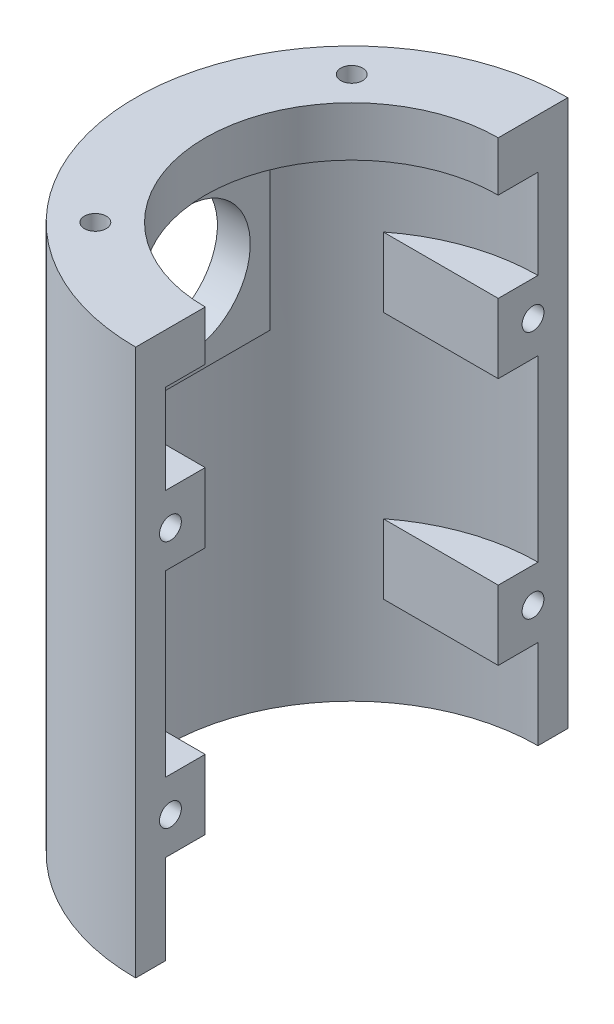
SolidWorks part; units mm, degrees
ref_plane "正面" through (0, 0, 0) normal (0, 0, 1) x (1, 0, 0)
ref_plane "平面" through (0, 0, 0) normal (0, 1, 0) x (1, 0, 0)
ref_plane "右側面" through (0, 0, 0) normal (1, 0, 0) x (0, 0, -1)
sketch "ｽｹｯﾁ1" plane through (0, 0, 0) normal (0, 1, 0) x (1, 0, 0)
  line L0 (0, -21.75) -> (0, -14.75)
  line L1 (0, -14.75) -> (0, 14.75) construction
  line L2 (0, 14.75) -> (0, 21.75)
  arc A0 (0, 21.75) -> (0, -21.75) centre (0, 0) ccw
  arc A1 (0, 14.75) -> (0, -14.75) centre (0, 0) ccw
  dimension "D1" = 14.75
  dimension "D2" = 7
extrude "ﾎﾞｽ - 押し出し1" add sketch "ｽｹｯﾁ1" along normal blind 55
sketch "ｽｹｯﾁ2" plane through (0, 55, 0) normal (0, 1, 0) x (1, 0, 0)
  circle A0 centre (0, 0) radius 14.75
  circle A1 centre (0, 0) radius 18.75
  arc A2 (0, 14.75) -> (0, -14.75) centre (0, 0) ccw construction
  arc A3 (0, 21.75) -> (0, -21.75) centre (0, 0) ccw construction
  dimension "D1" = 3
extrude "ｶｯﾄ - 押し出し1" cut sketch "ｽｹｯﾁ2" against normal through all from offset 5 offset against normal yes
sketch "ｽｹｯﾁ4" plane through (0, 0, 0) normal (1, 0, 0) x (0, 0, -1)
  line L0 (-14.75, 12.5) -> (-21.75, 12.5) construction
  line L1 (-21.75, 41) -> (-21.75, 34)
  line L2 (-18.75, 50) -> (-14.75, 50) construction
  line L3 (21.75, 55) -> (21.75, 0) construction
  line L4 (18.75, 50) -> (18.75, 0) construction
  line L5 (-21.75, 16) -> (-14.75, 16)
  line L6 (-14.75, 16) -> (-14.75, 9)
  line L7 (-14.75, 9) -> (-21.75, 9)
  line L8 (-21.75, 9) -> (-21.75, 16)
  line L9 (-21.75, 50) -> (21.75, 50) construction
  line L10 (0, 25) -> (-21.75, 25) construction
  line L11 (0, 25) -> (21.75, 25) construction
  line L12 (-21.75, 37.5) -> (21.75, 37.5) construction
  line L13 (-21.75, 0) -> (21.75, 0) construction
  line L14 (0, 50) -> (0, 0) construction
  line L15 (-18.25, 50) -> (-18.25, 0) construction
  line L16 (18.75, 50) -> (18.75, 37.5) construction
  line L17 (18.75, 37.5) -> (18.75, 25) construction
  line L18 (-21.75, 55) -> (-21.75, 0) construction
  line L19 (-21.75, 34) -> (-14.75, 34)
  line L20 (-14.75, 34) -> (-14.75, 41)
  line L21 (-14.75, 41) -> (-21.75, 41)
  line L22 (21.75, 9) -> (21.75, 16)
  line L23 (21.75, 16) -> (14.75, 16)
  line L24 (14.75, 16) -> (14.75, 9)
  line L25 (14.75, 9) -> (21.75, 9)
  line L26 (21.75, 34) -> (14.75, 34)
  line L27 (21.75, 41) -> (21.75, 34)
  line L28 (14.75, 41) -> (21.75, 41)
  line L29 (14.75, 34) -> (14.75, 41)
  circle A0 centre (-18.25, 37.5) radius 1.1 construction
  circle A1 centre (18.25, 37.5) radius 1.1 construction
  circle A2 centre (18.25, 12.5) radius 1.1 construction
  circle A3 centre (-18.25, 12.5) radius 1.1 construction
  dimension "D1" = 2.2
  dimension "D2" = 3.5
  dimension "D3" = 7
  dimension "D4" = 7
extrude "ﾎﾞｽ - 押し出し3" add sketch "ｽｹｯﾁ4" against normal up to next
sketch "ｽｹｯﾁ3" plane through (0, 0, 0) normal (1, 0, 0) x (0, 0, -1)
  line L0 (-21.75, 50) -> (21.75, 50) construction
  line L1 (0, 25) -> (-21.75, 25) construction
  line L2 (0, 25) -> (21.75, 25) construction
  line L3 (-21.75, 55) -> (-21.75, 0) construction
  line L4 (-21.75, 37.5) -> (21.75, 37.5) construction
  line L5 (21.75, 55) -> (21.75, 0) construction
  line L6 (-21.75, 0) -> (21.75, 0) construction
  line L7 (0, 50) -> (0, 0) construction
  line L8 (14.75, 50) -> (18.75, 50) construction
  line L9 (-18.25, 50) -> (-18.25, 0) construction
  line L10 (18.75, 50) -> (18.75, 37.5) construction
  line L11 (18.75, 37.5) -> (18.75, 25) construction
  line L12 (18.75, 50) -> (18.75, 41) construction
  circle A0 centre (-18.25, 37.5) radius 1.1
  circle A1 centre (18.25, 37.5) radius 1.1
  circle A2 centre (18.25, 12.5) radius 1.1
  circle A3 centre (-18.25, 12.5) radius 1.1
  dimension "D1" = 2.2
  dimension "D2" = 3.5
extrude "ｶｯﾄ - 押し出し2" cut sketch "ｽｹｯﾁ3" against normal blind 5
sketch "ｽｹｯﾁ5" plane through (0, 55, 0) normal (0, 1, 0) x (1, 0, 0)
  line L0 (0, 0) -> (-14.75, 0) construction
  line L1 (-14.75, 0) -> (-18.25, 0) construction
  line L2 (-18.25, 0) -> (-21.75, 0) construction
  line L3 (0, 0) -> (-12.9047, 12.9047) construction
  line L4 (-12.9047, -12.9047) -> (0, 0) construction
  circle A0 centre (0, 0) radius 18.25 construction
  arc A1 (0, 14.75) -> (0, -14.75) centre (0, 0) ccw construction
  arc A2 (0, 21.75) -> (0, -21.75) centre (0, 0) ccw construction
  circle A3 centre (-12.9047, -12.9047) radius 1.1
  circle A4 centre (-12.9047, 12.9047) radius 1.1
  dimension "D1" = 2.2
  dimension "D2" = 45
  dimension "D3" = 90
extrude "ｶｯﾄ - 押し出し3" cut sketch "ｽｹｯﾁ5" against normal up to vertex (5 mm away) up to point (0, 50, -14.75)
sketch "ｽｹｯﾁ6" plane through (0, 55, 0) normal (0, 1, 0) x (1, 0, 0)
  line L0 (-20.0203, 8.5) -> (-20.0203, -8.5)
  arc A0 (0, 21.75) -> (0, -21.75) centre (0, 0) ccw construction
  arc A1 (-20.0203, 8.5) -> (-20.0203, -8.5) centre (0, 0) ccw
  dimension "D1" = 17
extrude "ｶｯﾄ - 押し出し4" cut sketch "ｽｹｯﾁ6" against normal blind 17 from offset 5 offset against normal yes
sketch "ｽｹｯﾁ8" plane through (0, 50, 0) normal (0, -1, 0) x (1, 0, 0)
  line L0 (-16.7126, 8.5) -> (-16.7126, -8.5)
  arc A0 (-12.5377, -13.9417) -> (0, -18.75) centre (0, 0) ccw construction
  arc A1 (-16.7126, 8.5) -> (-16.7126, -8.5) centre (0, 0) ccw
  dimension "D1" = 17
extrude "ﾎﾞｽ - 押し出し4" add sketch "ｽｹｯﾁ8" along normal blind 17
sketch "ｽｹｯﾁ7" plane through (-20.0203, 0, 0) normal (-1, 0, 0) x (0, 0, 1)
  line L0 (8.5, 33) -> (-8.5, 50) construction
  line L2 (-8.5, 33) -> (8.5, 50) construction
  circle A0 centre (0, 41.5) radius 6.5
  dimension "D1" = 13
extrude "ｶｯﾄ - 押し出し5" cut sketch "ｽｹｯﾁ7" against normal through all
